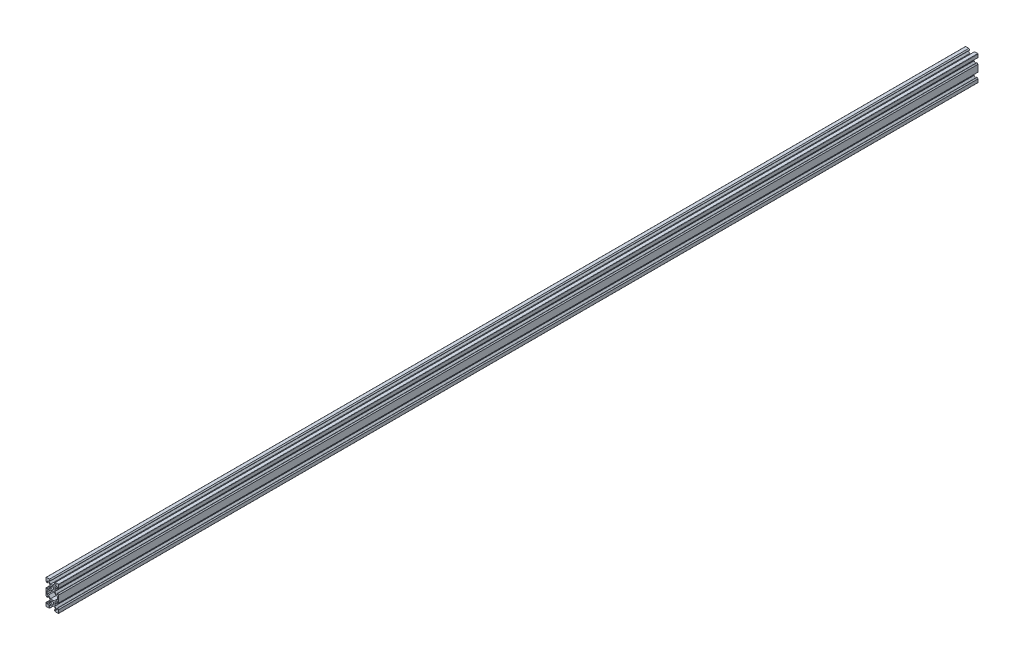
SolidWorks part; units mm, degrees
material "6061-T6 (SS)"
ref_plane "Front Plane" through (0, 0, 0) normal (0, 0, 1) x (1, 0, 0)
ref_plane "Top Plane" through (0, 0, 0) normal (0, 1, 0) x (1, 0, 0)
ref_plane "Right Plane" through (0, 0, 0) normal (1, 0, 0) x (0, 0, -1)
sketch "Sketch1" plane through (0, 0, 0) normal (0, 0, 1) x (1, 0, 0)
  line L0 (0, 0) -> (10, 0) construction
  line L1 (9.5, -20) -> (-9.5, -20)
  line L2 (10, -19.5) -> (10, 19.5)
  line L3 (9.5, 20) -> (-9.5, 20)
  line L4 (-10, -19.5) -> (-10, 19.5)
  line L5 (10, -20) -> (-10, 20) construction
  line L6 (10, 20) -> (-10, -20) construction
  circle A0 centre (0, 10) radius 2.1
  circle A1 centre (0, -10) radius 2.1
  arc A2 (-9.5, -20) -> (-10, -19.5) centre (-9.5, -19.5) cw
  arc A3 (9.5, -20) -> (10, -19.5) centre (9.5, -19.5) ccw
  arc A4 (10, 19.5) -> (9.5, 20) centre (9.5, 19.5) ccw
  arc A5 (-9.5, 20) -> (-10, 19.5) centre (-9.5, 19.5) ccw
  point P0 (0, 0)
  line B0 (0, 10) -> (0, 20) construction
  line B1 (0, 13.69) -> (-0.21, 13.9)
  line B2 (-0.21, 13.9) -> (-2.8393, 13.9)
  line B3 (-2.8393, 13.9) -> (-5.5, 16.5607)
  line B4 (-5.5, 16.5607) -> (-5.5, 18.2)
  line B5 (-5.5, 18.2) -> (-3.125, 18.2)
  line B6 (-3.125, 18.2) -> (-3.125, 18.545)
  line B7 (-3.125, 18.545) -> (-4.58, 20)
  line B8 (-4.58, 20) -> (4.58, 20)
  line B9 (0, 10) -> (-5.9132, 15.9132) construction
  line B10 (3.125, 18.545) -> (4.58, 20)
  line B11 (3.125, 18.2) -> (3.125, 18.545)
  line B12 (5.5, 18.2) -> (3.125, 18.2)
  line B13 (5.5, 16.5607) -> (5.5, 18.2)
  line B14 (2.8393, 13.9) -> (5.5, 16.5607)
  line B15 (0.21, 13.9) -> (2.8393, 13.9)
  line B16 (0, 13.69) -> (0.21, 13.9)
  line B17 (0, 10) -> (-10, 10) construction
  line B18 (-3.69, 10) -> (-3.9, 9.79)
  line B19 (-3.9, 9.79) -> (-3.9, 7.1607)
  line B20 (-3.9, 7.1607) -> (-6.5607, 4.5)
  line B21 (-6.5607, 4.5) -> (-8.2, 4.5)
  line B22 (-8.2, 4.5) -> (-8.2, 6.875)
  line B23 (-8.2, 6.875) -> (-8.545, 6.875)
  line B24 (-8.545, 6.875) -> (-10, 5.42)
  line B25 (-10, 5.42) -> (-10, 14.58)
  line B26 (0, 10) -> (-5.9132, 4.0868) construction
  line B27 (-8.545, 13.125) -> (-10, 14.58)
  line B28 (-8.2, 13.125) -> (-8.545, 13.125)
  line B29 (-8.2, 15.5) -> (-8.2, 13.125)
  line B30 (-6.5607, 15.5) -> (-8.2, 15.5)
  line B31 (-3.9, 12.8393) -> (-6.5607, 15.5)
  line B32 (-3.9, 10.21) -> (-3.9, 12.8393)
  line B33 (-3.69, 10) -> (-3.9, 10.21)
  line B34 (0, -10) -> (-10, -10) construction
  line B35 (-3.69, -10) -> (-3.9, -10.21)
  line B36 (-3.9, -10.21) -> (-3.9, -12.8393)
  line B37 (-3.9, -12.8393) -> (-6.5607, -15.5)
  line B38 (-6.5607, -15.5) -> (-8.2, -15.5)
  line B39 (-8.2, -15.5) -> (-8.2, -13.125)
  line B40 (-8.2, -13.125) -> (-8.545, -13.125)
  line B41 (-8.545, -13.125) -> (-10, -14.58)
  line B42 (-10, -14.58) -> (-10, -5.42)
  line B43 (0, -10) -> (-5.9132, -15.9132) construction
  line B44 (-8.545, -6.875) -> (-10, -5.42)
  line B45 (-8.2, -6.875) -> (-8.545, -6.875)
  line B46 (-8.2, -4.5) -> (-8.2, -6.875)
  line B47 (-6.5607, -4.5) -> (-8.2, -4.5)
  line B48 (-3.9, -7.1607) -> (-6.5607, -4.5)
  line B49 (-3.9, -9.79) -> (-3.9, -7.1607)
  line B50 (-3.69, -10) -> (-3.9, -9.79)
  line B51 (0, -10) -> (0, -20) construction
  line B52 (0, -13.69) -> (0.21, -13.9)
  line B53 (0.21, -13.9) -> (2.8393, -13.9)
  line B54 (2.8393, -13.9) -> (5.5, -16.5607)
  line B55 (5.5, -16.5607) -> (5.5, -18.2)
  line B56 (5.5, -18.2) -> (3.125, -18.2)
  line B57 (3.125, -18.2) -> (3.125, -18.545)
  line B58 (3.125, -18.545) -> (4.58, -20)
  line B59 (4.58, -20) -> (-4.58, -20)
  line B60 (0, -10) -> (5.9132, -15.9132) construction
  line B61 (-3.125, -18.545) -> (-4.58, -20)
  line B62 (-3.125, -18.2) -> (-3.125, -18.545)
  line B63 (-5.5, -18.2) -> (-3.125, -18.2)
  line B64 (-5.5, -16.5607) -> (-5.5, -18.2)
  line B65 (-2.8393, -13.9) -> (-5.5, -16.5607)
  line B66 (-0.21, -13.9) -> (-2.8393, -13.9)
  line B67 (0, -13.69) -> (-0.21, -13.9)
  line B68 (0, -10) -> (10, -10) construction
  line B69 (3.69, -10) -> (3.9, -9.79)
  line B70 (3.9, -9.79) -> (3.9, -7.1607)
  line B71 (3.9, -7.1607) -> (6.5607, -4.5)
  line B72 (6.5607, -4.5) -> (8.2, -4.5)
  line B73 (8.2, -4.5) -> (8.2, -6.875)
  line B74 (8.2, -6.875) -> (8.545, -6.875)
  line B75 (8.545, -6.875) -> (10, -5.42)
  line B76 (10, -5.42) -> (10, -14.58)
  line B77 (0, -10) -> (5.9132, -4.0868) construction
  line B78 (8.545, -13.125) -> (10, -14.58)
  line B79 (8.2, -13.125) -> (8.545, -13.125)
  line B80 (8.2, -15.5) -> (8.2, -13.125)
  line B81 (6.5607, -15.5) -> (8.2, -15.5)
  line B82 (3.9, -12.8393) -> (6.5607, -15.5)
  line B83 (3.9, -10.21) -> (3.9, -12.8393)
  line B84 (3.69, -10) -> (3.9, -10.21)
  line B85 (0, 10) -> (10, 10) construction
  line B86 (3.69, 10) -> (3.9, 10.21)
  line B87 (3.9, 10.21) -> (3.9, 12.8393)
  line B88 (3.9, 12.8393) -> (6.5607, 15.5)
  line B89 (6.5607, 15.5) -> (8.2, 15.5)
  line B90 (8.2, 15.5) -> (8.2, 13.125)
  line B91 (8.2, 13.125) -> (8.545, 13.125)
  line B92 (8.545, 13.125) -> (10, 14.58)
  line B93 (10, 14.58) -> (10, 5.42)
  line B94 (0, 10) -> (5.9132, 15.9132) construction
  line B95 (8.545, 6.875) -> (10, 5.42)
  line B96 (8.2, 6.875) -> (8.545, 6.875)
  line B97 (8.2, 4.5) -> (8.2, 6.875)
  line B98 (6.5607, 4.5) -> (8.2, 4.5)
  line B99 (3.9, 7.1607) -> (6.5607, 4.5)
  line B100 (3.9, 9.79) -> (3.9, 7.1607)
  line B101 (3.69, 10) -> (3.9, 9.79)
  line B102 (-8.2, -2.7) -> (-8.2, 2.7)
  line B103 (-8.2, 2.7) -> (-6.2393, 2.7)
  line B104 (-6.2393, 2.7) -> (-2.8393, 6.1)
  line B105 (-2.8393, 6.1) -> (2.8393, 6.1)
  line B106 (0, 6.1) -> (0, 0) construction
  line B107 (0, 0) -> (-8.2, 0) construction
  line B108 (6.2393, 2.7) -> (2.8393, 6.1)
  line B109 (8.2, 2.7) -> (6.2393, 2.7)
  line B110 (8.2, -2.7) -> (8.2, 2.7)
  line B111 (8.2, -2.7) -> (6.2393, -2.7)
  line B112 (6.2393, -2.7) -> (2.8393, -6.1)
  line B113 (-2.8393, -6.1) -> (2.8393, -6.1)
  line B114 (-6.2393, -2.7) -> (-2.8393, -6.1)
  line B115 (-8.2, -2.7) -> (-6.2393, -2.7)
  line B116 (0, 6.1) -> (0, 10) construction
  line B117 (0, 10) -> (-5.0927, 4.9073) construction
  dimension "D4" = 4.2
  dimension "D5" = 0.5
  dimension "D1" = 20
  dimension "D2" = 40
  dimension "D3" = 20
sketch_block_instance "V Slot 1-4"
sketch_block "V Slot 1" parameters "D1"=10, "D2"=11, "D3"=4.3, "D4"=1.8, "D5"=0.21, "D6"=45, "D7"=9.16, "D8"=1.5, "D9"=6.25
sketch_block_instance "V Slot 1-5"
sketch_block_instance "V Slot 1-6"
sketch_block_instance "V Slot 1-7"
sketch_block_instance "V Slot 1-8"
sketch_block_instance "V Slot 1-9"
sketch_block_instance "Center Cutout 1-1"
sketch_block "Center Cutout 1" parameters "D1"=5.4, "D2"=12.2, "D3"=8.2, "D4"=45, "D5"=10, "D6"=1.5
extrude "Boss-Extrude1" add sketch "Sketch1" along normal blind 1455 contours B101 B86 B87 B88 B89 B90 B91 B92 L2 A4 L3 B10 B11 B12 B13 B14 B15 B16 B1 B2 B3 B4 B5 B6 B7 A5 L4 B27 B28 B29 B30 B31 B32 B33 B18 B19 B20 B21 B22 B23 B24 B44 B45 B46 B47 B48 B49 B50 B35 region at (7.04, -19.5528, 0)
